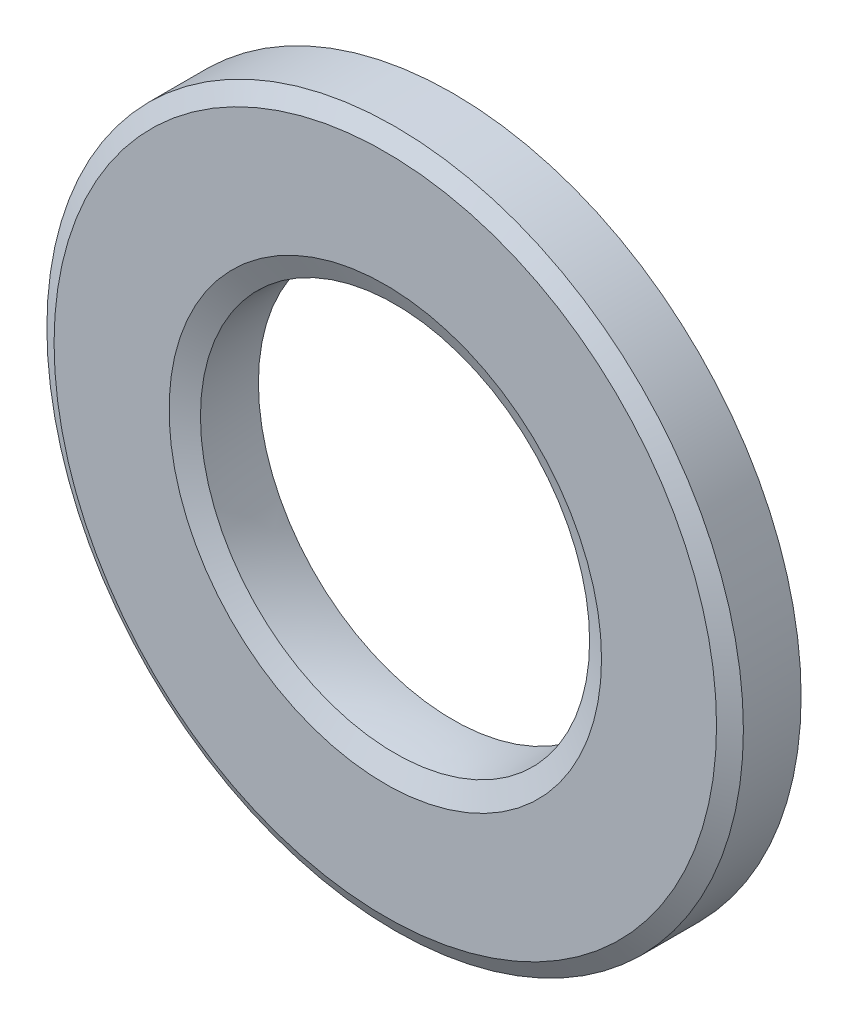
SolidWorks part; units mm, degrees
other "Imported1" parameters "D1"=0.254
material "Commercial Bronze, UNS C22000 (90-10 Bronze)"
ref_plane "Front Plane" through (0, 0, 0) normal (0, 0, 1) x (1, 0, 0)
ref_plane "Top Plane" through (0, 0, 0) normal (0, 1, 0) x (1, 0, 0)
ref_plane "Right Plane" through (0, 0, 0) normal (1, 0, 0) x (0, 0, -1)
sketch "Sketch1" plane through (0, 0, 0) normal (0, 0, 1) x (1, 0, 0)
  line L0 (-9, 0) -> (9, 0) construction
  line L1 (-5, 0) -> (5, 0) construction
  circle A0 centre (0, 0) radius 5 construction
  circle A1 centre (0, 0) radius 9 construction
  point P8 (0, 0)
  point P9 (0, 9)
  point P11 (5, 0)
  dimension "ID" = 10
  dimension "OD" = 18
sketch "Sketch2" plane through (0, 0, 0) normal (1, 0, 0) x (0, 0, -1)
  line L0 (-1, 9) -> (1, 9) construction
  point P2 (0, 9)
  dimension "Thickness" = 2
sketch "Sketch3" plane through (0, 0, 0) normal (0, 0, 1) x (1, 0, 0)
  circle A0 centre (0, 0) radius 5
  circle A1 centre (0, 0) radius 9
extrude "Boss-Extrude1" add sketch "Sketch3" along normal up to vertex (1 mm away) and the other way up to vertex (1 mm away) up to point (0, 9, 1) other way up to point (0, 9, -1)
chamfer "Chamfer1" distance 0.254 angle 60 2 edges at (9, 0, -1) (9, 0, 1)
sketch "Sketch4" plane through (0, 0, 0) normal (1, 0, 0) x (0, 0, -1)
  line L3 (-1, 4.9492) -> (-1, 5.0508)
  line L4 (-1, 4.9492) -> (1, 4.9492)
  line L5 (1, 4.9492) -> (1, 5.0508)
  line L6 (-1, 0) -> (1, 0) construction
  arc A0 (-1, 5.0508) -> (1, 5.0508) centre (0, 14.8679) ccw
  point P0 (0, 5)
  point P9 (-1, 5)
  point P13 (0, 0)
  dimension "D1" = 0.0508
revolve "Cut-Revolve1" cut sketch "Sketch4" angle 360 about L6
chamfer "Chamfer2" distance 0.254 angle 60 2 edges at (0, -5.0508, -1) (0, -5.0508, 1)
equation "\"D1@Chamfer2\"=\"D1@Chamfer1\""
